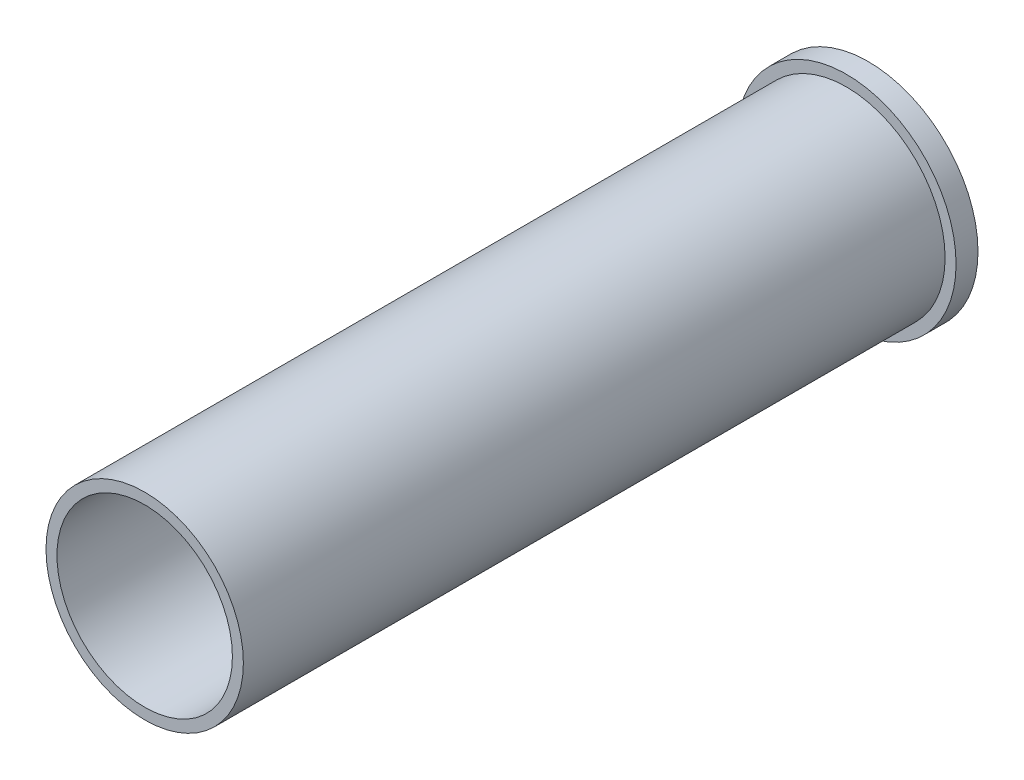
SolidWorks part; units mm, degrees
ref_plane "Front Plane" through (0, 0, 0) normal (0, 0, 1) x (1, 0, 0)
ref_plane "Top Plane" through (0, 0, 0) normal (0, 1, 0) x (1, 0, 0)
ref_plane "Right Plane" through (0, 0, 0) normal (1, 0, 0) x (0, 0, -1)
sketch "Sketch1" plane through (0, 0, 0) normal (0, 0, 1) x (1, 0, 0)
  circle A0 centre (0, 0) radius 50.8
  circle A1 centre (0, 0) radius 57.15
  circle A2 centre (0, 0) radius 63.5
  dimension "D1" = 127
  dimension "D2" = 114.3
  dimension "D3" = 101.6
extrude "Boss-Extrude1" add sketch "Sketch1" against normal blind 12.7 contours A2 A1 | A1 A0 region at (-55.5336, 0, 0) region at (-61.7039, 0, 0)
extrude "Boss-Extrude2" add sketch "Sketch1<3>" along normal blind 406.4 contours A1 A0 region at (-55.5336, 0, 0)
sketch "Sketch1<3>" plane through (0, 0, 0) normal (0, 0, 1) x (1, 0, 0) same geometry as "Sketch1"
